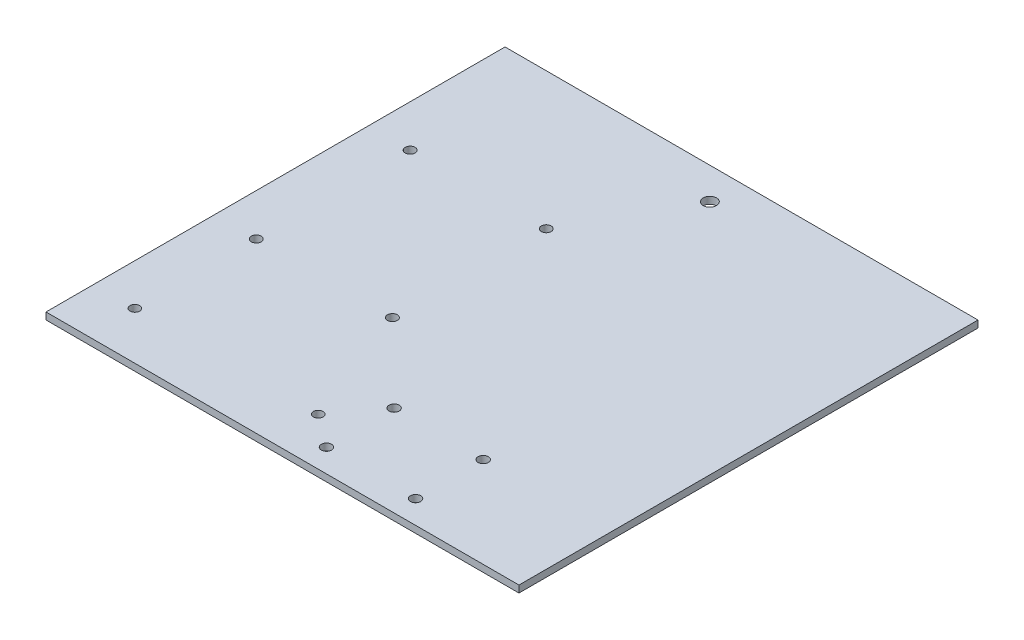
SolidWorks part; units mm, degrees
ref_plane "Front Plane" through (0, 0, 0) normal (0, 0, 1) x (1, 0, 0)
ref_plane "Top Plane" through (0, 0, 0) normal (0, 1, 0) x (1, 0, 0)
ref_plane "Right Plane" through (0, 0, 0) normal (1, 0, 0) x (0, 0, -1)
sketch "Sketch1" plane through (0, 0, 0) normal (0, 1, 0) x (1, 0, 0)
  line L1 (-94.869, -92.075) -> (94.869, -92.075)
  line L2 (-94.869, -92.075) -> (-94.869, 92.075)
  line L3 (-94.869, 92.075) -> (94.869, 92.075)
  line L4 (94.869, -92.075) -> (94.869, 92.075)
  line L5 (-94.869, -92.075) -> (94.869, 92.075) construction
  line L6 (-94.869, 92.075) -> (94.869, -92.075) construction
  point P0 (0, 0)
  dimension "D1" = 189.738
  dimension "D2" = 184.15
extrude "Boss-Extrude1" add sketch "Sketch1" along normal blind 2.794
sketch "Sketch2" plane through (0, 2.794, 0) normal (0, 1, 0) x (1, 0, 0)
  line L2 (94.869, 92.075) -> (-94.869, 92.075) construction
  circle A0 centre (0, 79.375) radius 2.6797
  point P4 (0, 92.075)
  dimension "D1" = 5.3594
  dimension "D2" = 12.7
extrude "Cut-Extrude1" cut sketch "Sketch2" against normal through all
sketch "Sketch4" plane through (0, 2.794, 0) normal (0, 1, 0) x (1, 0, 0)
  line L7 (5.481, -52.725) -> (46.661, -52.725) construction
  line L8 (5.481, -52.725) -> (5.481, -85.725) construction
  line L9 (5.481, -85.725) -> (46.661, -85.725) construction
  line L10 (46.661, -52.725) -> (46.661, -85.725) construction
  line L11 (5.481, -52.725) -> (46.661, -85.725) construction
  line L12 (5.481, -85.725) -> (46.661, -52.725) construction
  line L13 (-82.169, -47.405) -> (-0.869, -47.405) construction
  line L14 (-82.169, -47.405) -> (-82.169, -98.425) construction
  line L15 (-82.169, -98.425) -> (-0.869, -98.425) construction
  line L16 (-0.869, -47.405) -> (-0.869, -98.425) construction
  line L17 (-82.169, -47.405) -> (-0.869, -98.425) construction
  line L18 (-82.169, -98.425) -> (-0.869, -47.405) construction
  line L19 (5.481, -69.225) -> (46.661, -69.225) construction
  line L24 (-94.869, 92.075) -> (-94.869, -92.075) construction
  line L25 (-94.869, -92.075) -> (94.869, -92.075) construction
  line L34 (-82.169, 53.685) -> (-19.299, 53.685) construction
  line L41 (-82.169, 53.685) -> (-82.169, -41.055) construction
  line L42 (-82.169, -41.055) -> (-19.299, -41.055) construction
  line L43 (-19.299, 53.685) -> (-19.299, -41.055) construction
  circle A2 centre (-78.2965, -72.9925) radius 1.9362
  circle A3 centre (-4.7415, -72.9925) radius 1.9362
  circle A4 centre (8.356, -55.65) radius 2.0487
  circle A5 centre (44.106, -55.65) radius 2.0487
  circle A6 centre (44.106, -82.8) radius 2.0487
  circle A7 centre (8.356, -82.8) radius 2.0487
  circle A16 centre (-78.039, 37.175) radius 1.98
  circle A21 centre (-23.429, 37.175) radius 1.98
  circle A22 centre (-23.429, -24.545) radius 1.98
  circle A23 centre (-78.039, -24.545) radius 1.98
  point P2 (-76.4969, 53.685)
  point P11 (26.071, -69.225)
  point P16 (-41.519, -72.915)
  dimension "D13" = 3.8724
  dimension "D15" = 3.8724
  dimension "D20" = 4.0974
  dimension "D24" = 6.35
  dimension "D30" = 2
  dimension "D31" = 2
  dimension "D32" = 16.51
  dimension "D29" = 3.96
  dimension "D35" = 4.13
  dimension "D36" = 4.13
  dimension "D38" = 16.51
  dimension "D39" = 4.13
  dimension "D40" = 6.35
  dimension "D8" = 41.18
  dimension "D9" = 33
  dimension "D10" = 81.3
  dimension "D11" = 51.02
  dimension "D12" = 12.7
  dimension "D14" = 25.4325
  dimension "D16" = 25.4325
  dimension "D17" = 3.8725
  dimension "D18" = 3.8725
  dimension "D19" = 35.75
  dimension "D21" = 2.925
  dimension "D22" = 2.555
  dimension "D23" = 16.5
  dimension "D25" = 6.35
  dimension "D26" = 6.35
  dimension "D27" = 94.74
  dimension "D28" = 62.87
  dimension "D41" = 12.7
extrude "Cut-Extrude3" cut sketch "Sketch4" against normal through all contours A3 | A2 | A5 | A4 | A7 | A6 | A22 | A23 | A16 | A21
